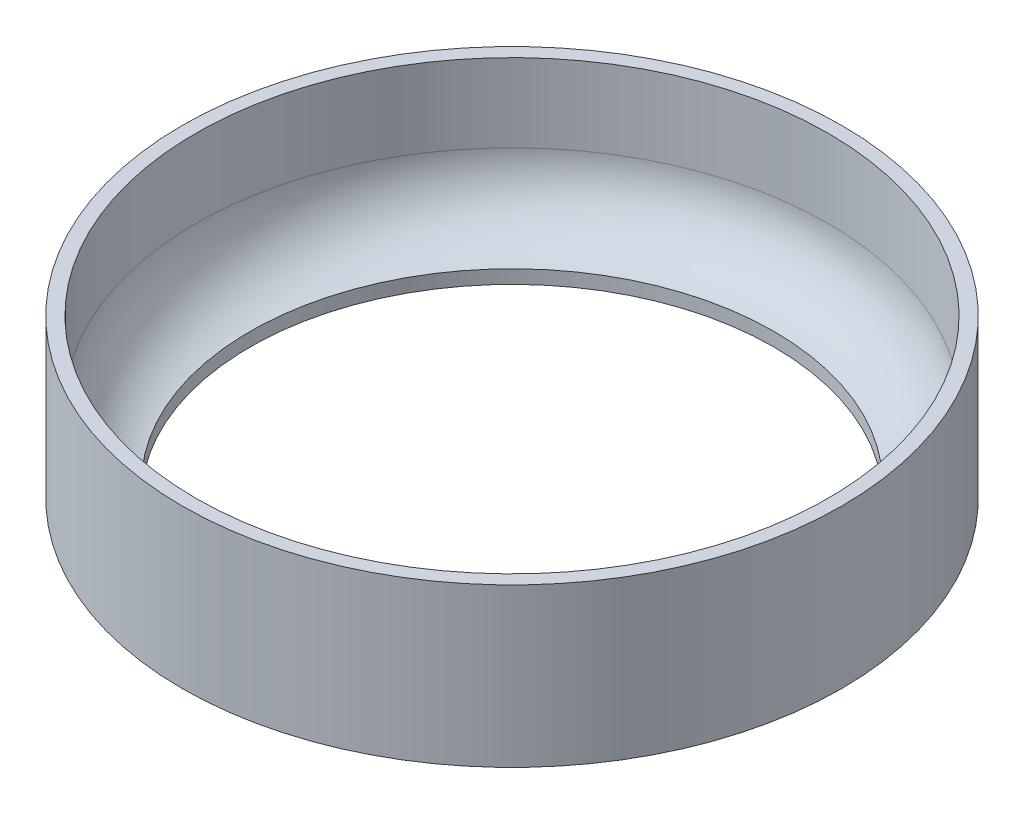
SolidWorks part; units mm, degrees
ref_plane "Front Plane" through (0, 0, 0) normal (0, 0, 1) x (1, 0, 0)
ref_plane "Top Plane" through (0, 0, 0) normal (0, 1, 0) x (1, 0, 0)
ref_plane "Right Plane" through (0, 0, 0) normal (1, 0, 0) x (0, 0, -1)
sketch "Sketch1" plane through (0, 0, 0) normal (0, 0, 1) x (1, 0, 0)
  line L0 (-73, 0) -> (73, 0) construction
  line L1 (73, 35) -> (73, 0)
  line L2 (73, 0) -> (58, 0)
  line L4 (70, 3) -> (70, 35)
  line L5 (70, 35) -> (73, 35)
  line L6 (58, 0) -> (58, 3)
  line L7 (58, 3) -> (70, 3)
  line L8 (0, 0) -> (0, 35.2286) construction
  point P4 (0, 0)
  dimension "D1" = 146
  dimension "D2" = 15
  dimension "D3" = 3
  dimension "D4" = 3
  dimension "D5" = 35
revolve "Revolve1" add sketch "Sketch1" angle 360 about L8
fillet "Fillet1" radius 15 1 edges at (0, 3, -70)
